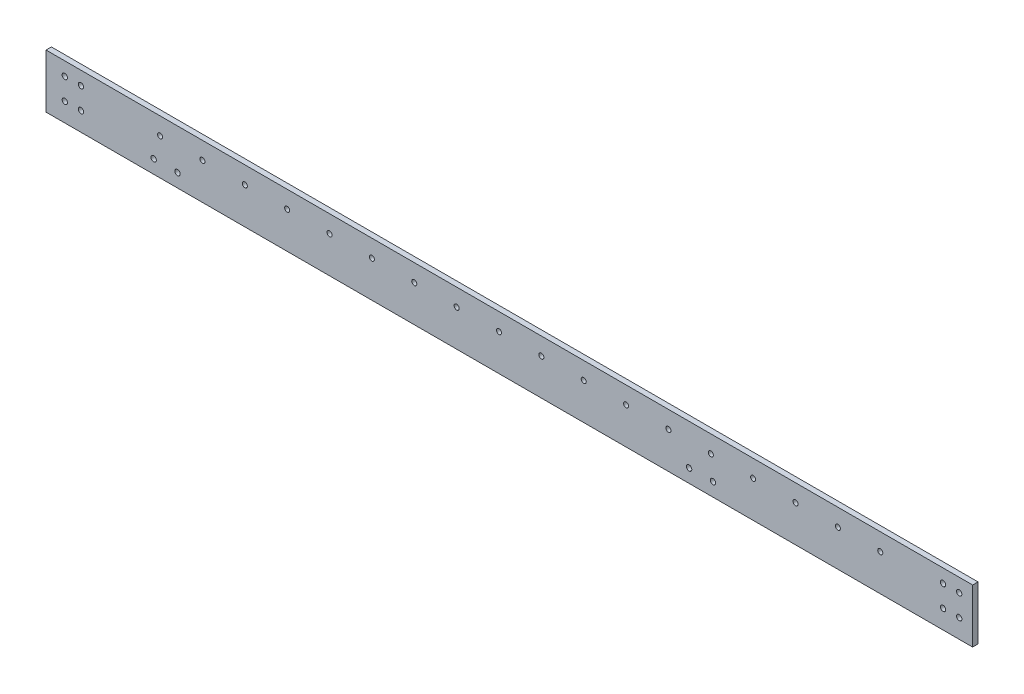
SolidWorks part; units mm, degrees
ref_plane "Front Plane" through (0, 0, 0) normal (0, 0, 1) x (1, 0, 0)
ref_plane "Top Plane" through (0, 0, 0) normal (0, 1, 0) x (1, 0, 0)
ref_plane "Right Plane" through (0, 0, 0) normal (1, 0, 0) x (0, 0, -1)
sketch "Sketch1" plane through (0, 0, 0) normal (1, 0, 0) x (0, 0, -1)
  line L0 (0, 0) -> (-3.175, 0)
  line L3 (-3.175, 0) -> (-3.175, 31.75)
  line L4 (-3.175, 31.75) -> (0, 31.75)
  line L5 (0, 31.75) -> (0, 0)
  dimension "LHeight" = 31.75
  dimension "LMaterialThickness" = 3.175
extrude "Boss-Extrude1" add sketch "Sketch1" along normal blind 546.825
sketch "LeftSideHoles-Sketch4" plane through (0, 0, 3.175) normal (0, 0, 1) x (1, 0, 0)
  line L0 (546.825, 31.75) -> (546.825, 0) construction
  line L1 (0, 31.75) -> (0, 0) construction
  line L2 (546.825, 31.75) -> (546.825, 0) construction
  line L3 (546.825, 31.75) -> (0, 31.75) construction
  line L4 (546.825, 0) -> (0, 0) construction
  line L5 (546.825, 31.75) -> (0, 31.75) construction
  line L6 (0, 31.75) -> (0, 0) construction
  circle A1 centre (11.1125, 23.8125) radius 1.5875
  circle A3 centre (529.3625, 23.8125) radius 1.5875
  circle A4 centre (20.6375, 23.8125) radius 1.5875
  circle A5 centre (538.8875, 23.8125) radius 1.5875
  circle A6 centre (11.1125, 11.1125) radius 1.5875
  circle A7 centre (20.6375, 11.1125) radius 1.5875
  circle A8 centre (529.3625, 11.1125) radius 1.5875
  circle A9 centre (538.8875, 11.1125) radius 1.5875
  circle A10 centre (492.325, 21.525) radius 1.5
  circle A11 centre (467.325, 21.525) radius 1.5
  circle A12 centre (442.325, 21.525) radius 1.5
  circle A13 centre (417.325, 21.525) radius 1.5
  circle A14 centre (392.325, 21.525) radius 1.5
  circle A15 centre (367.325, 21.525) radius 1.5
  circle A16 centre (342.325, 21.525) radius 1.5
  circle A17 centre (317.325, 21.525) radius 1.5
  circle A18 centre (292.325, 21.525) radius 1.5
  circle A19 centre (267.325, 21.525) radius 1.5
  circle A20 centre (242.325, 21.525) radius 1.5
  circle A21 centre (217.325, 21.525) radius 1.5
  circle A22 centre (192.325, 21.525) radius 1.5
  circle A23 centre (167.325, 21.525) radius 1.5
  circle A24 centre (142.325, 21.525) radius 1.5
  circle A25 centre (117.325, 21.525) radius 1.5
  circle A26 centre (92.325, 21.525) radius 1.5
  circle A27 centre (67.325, 21.525) radius 1.5
  circle A28 centre (77.6375, 7.9375) radius 1.5875
  circle A29 centre (379.5125, 7.9375) radius 1.5875
  circle A30 centre (63.5125, 7.9375) radius 1.5875
  circle A31 centre (393.6375, 7.9375) radius 1.5875
  dimension "D2" = 3.175
  dimension "D10" = 3
  dimension "D14" = 3.175
  dimension "D4" = 7.9375
  dimension "D1" = 11.1125
  dimension "D6" = 20.6375
  dimension "D3" = 7.9375
  dimension "D5" = 17.4625
  dimension "D7" = 11.1125
  dimension "D8" = 54.5
  dimension "D9" = 10.225
  dimension "D12" = 25
  dimension "D13" = 7.9375
  dimension "D15" = 77.6375
  dimension "D18" = 14.125
  dimension "D16" = 14.125
  dimension "D17" = 316
  dimension "D11" = 18
extrude "LeftSideHoles-Cut-Extrude3" cut sketch "LeftSideHoles-Sketch4" against normal through all
equation "\"RailThickness\"= .125in'Spec"
equation "\"SideRailHoleY1FromEdge\"= \"HoleOffsetFromEdge\""
equation "\"SideRailHoleX1FromSide\"= \"HoleOffsetFromSide\""
equation "\"MidSideRailLength\"= \"SideRailLength\" - \"RailThickness\"'Equals 546.825 => MidSideRail buts up against MidBackRail"
equation "\"VSWidth\"= 1.25in'Spec"
equation "\"HoleOffsetFromEdge\"= \"RailThickness\" * 2.5"
equation "\"HoleOffsetFromSide\"= \"RailThickness\" * 3.5"
equation "\"SideRailHoleX2FromSide\"= \"VSWidth\" - \"HoleOffsetFromEdge\" - \"RailThickness\"'Equals 20.6375"
equation "\"FasteningHoleDiameter\"= .125in"
equation "\"D2@LeftSideHoles-Sketch4\" = \"FasteningHoleDiameter\""
equation "\"LHeight@Sketch1\"=\"MidSideRailHeight\""
equation "\"LMaterialThickness@Sketch1\"=\"RailThickness\""
equation "\"D1@Boss-Extrude1\"=\"MidSideRailLength\""
equation "\"D4@LeftSideHoles-Sketch4\" = \"SideRailHoleY1FromEdge\""
equation "\"D1@LeftSideHoles-Sketch4\"=\"SideRailHoleX1FromSide\""
equation "\"D6@LeftSideHoles-Sketch4\"=\"SideRailHoleX2FromSide\" "
equation "\"D3@LeftSideHoles-Sketch4\"=\"SideRailHoleX1FromSide\" - \"RailThickness\""
equation "\"D5@LeftSideHoles-Sketch4\"=\"SideRailHoleX2FromSide\" - \"RailThickness\""
equation "\"D7@LeftSideHoles-Sketch4\"=\"HoleOffsetFromSide\""
equation "\"LinearRailXMountHole\"= \"StepperWidth\" + \"LinearRailFirstHoleOffsetFromEdge\""
equation "\"D8@LeftSideHoles-Sketch4\"=\"LinearRailXMountHole\""
equation "\"D9@LeftSideHoles-Sketch4\"=\"V6.3 GantryMiddleToToTopOfMidSideRail\""
equation "\"LinearRailHoleDistance\"= 25mm'Spec"
equation "\"D12@LeftSideHoles-Sketch4\"=\"LinearRailHoleDistance\""
equation "\"LinearRailFirstHoleOffsetFromEdge\"= 12.5mm'Spec"
equation "\"SideRailLength\"= 550mm"
equation "\"MidSideRailHeight\"= 1.25in"
equation "\"StepperWidth\"= 42mm'Spec"
equation "\"StepperHolePadSize\"= \"StepperHoleDiameter\""
equation "\"D13@LeftSideHoles-Sketch4\"=\"HoleOffsetFromEdge\""
equation "\"D14@LeftSideHoles-Sketch4\"=\"FasteningHoleDiameter\""
equation "\"D18@LeftSideHoles-Sketch4\"=\"RodStabilizerDepth\" - \"HoleOffsetFromEdge\" * 2"
equation "\"DistanceFromBedFrontToFirstLeftStepperHole\"= \"LeadScrewNutPadSize\" + 10mm'Equals 34"
equation "\"BeltTensionerDepth\"= \"BeltTensionerBackWallThickness\" + \"BeltTensionerInnerDepth\"'Equals 23.4"
equation "\"20TGT2PulleyDiameter\"= 17.9mm'Spec"
equation "\"BeltTensionerSpaceBetweenPulleyAndWall\"= 1.5mm"
equation "\"BeltTensionerBackWallThickness\"= 4mm"
equation "\"BeltTensionerInnerDepth\"= \"20TGT2PulleyDiameter\" + \"BeltTensionerSpaceBetweenPulleyAndWall\""
equation "\"DistanceFromFrontSideToBedFront\"= \"RailThickness\" + \"BeltTensionerDepth\" + 10mm'Equals 36.575"
equation "\"DistanceFromFrontSideToFirstLeftStepperHole\"= \"DistanceFromFrontSideToBedFront\" + \"DistanceFromBedFrontToFirstLeftStepperHole\"'Equals 70.575"
equation "\"DistanceBetweenFrontToBackStepperHoles\"= \"BedLength\" - \"DistanceFromBedFrontToFirstLeftStepperHole\"'Equals 316"
equation "\"BedLength\"= \"BedInnerSquareLength\" + \"BedLWidth\" * 2 - \"BedOverlap\" * 2 + \"BedIncreasedByLength\"'Equals 350"
equation "\"BedOverlap\"= 20mm"
equation "\"BedThirdSize\"= 70mm"
equation "\"BedInnerSquareWidth\"= \"BedThirdSize\" * 3'Equals 210"
equation "\"BedLWidth\"= \"BedThirdSize\" + \"BedOverlap\"'Equals 90"
equation "\"BedIncreasedByLength\"= 0mm"
equation "\"LM8UUDiameter\"= 15mm"
equation "\"RodStabilizerDepth\"= \"LM8UUDiameter\" * 2"
equation "\"BedInnerSquareLength\"= \"BedInnerSquareWidth\""
equation "\"DistanceFromFrontSideToFirstLeftStabilizerMountingHole\"= \"DistanceFromFrontSideToFirstLeftStepperHole\" + \"RodStabilizerDepth\" / 2 - \"HoleOffsetFromEdge\"'Equals 77.6375"
equation "\"D15@LeftSideHoles-Sketch4\"=\"DistanceFromFrontSideToFirstLeftStabilizerMountingHole\""
equation "\"D17@LeftSideHoles-Sketch4\"=\"DistanceBetweenFrontToBackStepperHoles\""
equation "\"GABMidWallHeight\"= 28mm'Must equal 28 or changes alignment"
equation "\"20TGT2PulleyWidth\"= 8.7mm'The STL of the Pulley in the diagram is a bit larger"
equation "\"GABMidShortRiserHeight\"= \"GABMidWallHeight\" / 2 - \"20TGT2PulleyWidth\"'Equals 5.3"
equation "\"D16@LeftSideHoles-Sketch4\"=\"RodStabilizerDepth\" - \"HoleOffsetFromEdge\"*2"
equation "\"GABUpperHeight\"= 6mm"
equation "\"GABLowerHeight\"= 3mm"
equation "\"GABHeight\"= \"GABLowerHeight\" + \"GABMidWallHeight\" + \"GABUpperHeight\""
equation "\"GABRiserBossOffset\"= 0.8mm'Aligns Pulleys"
equation "\"StepperShaftLength\"= 24mm'Pulley will be attached to the end"
equation "\"V6.1 FromGantryPulleyToGantryMiddle\"= \"GABHeight\" / 2 - \"GABMidShortRiserHeight\" - \"GABLowerHeight\" + \"GABRiserBossOffset\" / 2"
equation "\"V6.2 GantryMiddleToTopOfMidBackRail\"= \"StepperShaftLength\" - \"V6.1 FromGantryPulleyToGantryMiddle\""
equation "\"V6.3 GantryMiddleToToTopOfMidSideRail\"= \"V6.2 GantryMiddleToTopOfMidBackRail\" - \"RailThickness\""
equation "\"LeadScrewNutMountingHoleFlangeDiameter\"= 22mm'Spec"
equation "\"LeadScrewNutPadSize\"= \"LeadScrewNutMountingHoleFlangeDiameter\" + 2mm'Equals 24"
